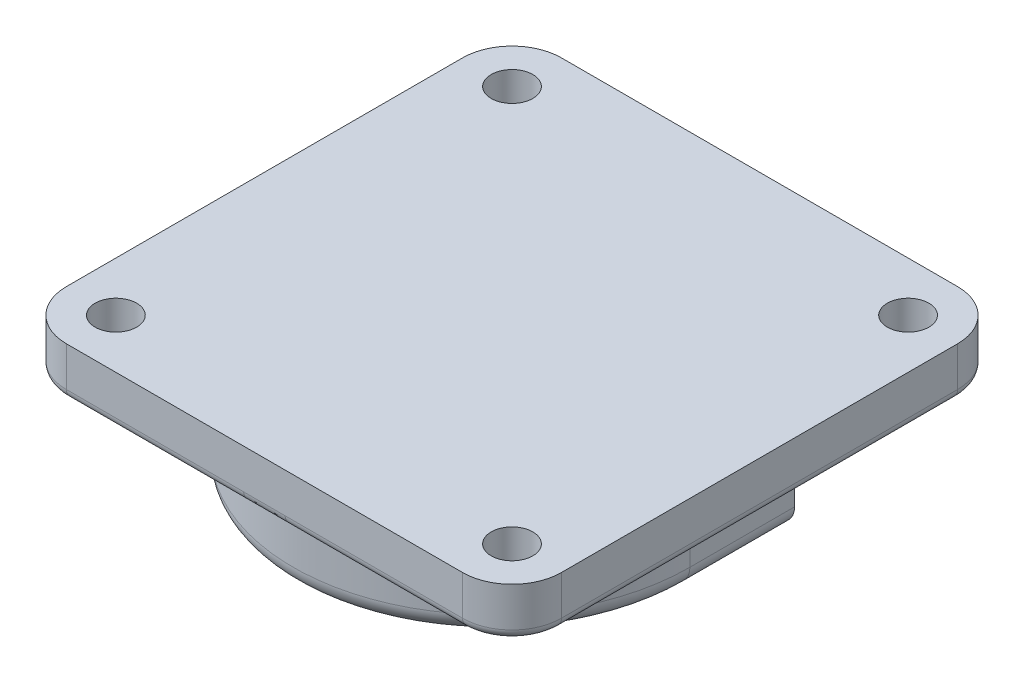
SolidWorks part; units mm, degrees
ref_plane "Front Plane" through (0, 0, 0) normal (0, 0, 1) x (1, 0, 0)
ref_plane "Top Plane" through (0, 0, 0) normal (0, 1, 0) x (1, 0, 0)
ref_plane "Right Plane" through (0, 0, 0) normal (1, 0, 0) x (0, 0, -1)
sketch "Sketch1" plane through (0, 0, 0) normal (0, 1, 0) x (1, 0, 0)
  line L0 (0, 11.4059) -> (0, -65.5477)
  line L1 (-20, 0) -> (20, 0)
  line L2 (17.052, -27.0709) -> (17.052, -16.496)
  line L3 (-20, -50) -> (20, -50)
  line L4 (25, -5) -> (25, -45)
  line L5 (17.052, -16.496) -> (20.0291, -16.496)
  line L6 (20.0291, -16.496) -> (20.0291, -27.0709)
  line L7 (-17.052, -16.496) -> (-20.0291, -16.496)
  line L8 (-25, -5) -> (-25, -45)
  line L9 (-17.052, -27.0709) -> (-17.052, -16.496)
  line L10 (-20.0291, -16.496) -> (-20.0291, -27.0709)
  arc A0 (25, -5) -> (20, 0) centre (20, -5) ccw
  circle A1 centre (20, -5) radius 2.1
  arc A2 (25, -45) -> (20, -50) centre (20, -45) cw
  circle A3 centre (20, -45) radius 2.1
  arc A4 (-17.052, -27.0709) -> (17.052, -27.0709) centre (0, -27.0709) ccw
  arc A5 (-20.0291, -27.0709) -> (20.0291, -27.0709) centre (0, -27.0709) ccw
  circle A6 centre (-20, -45) radius 2.1
  arc A7 (-25, -45) -> (-20, -50) centre (-20, -45) ccw
  circle A8 centre (-20, -5) radius 2.1
  arc A9 (-25, -5) -> (-20, 0) centre (-20, -5) cw
  point P2 (0, 0)
  point P30 (0, -50)
  dimension "D1" = 5
  dimension "D2" = 5
extrude "Boss-Extrude1" add sketch "Sketch1" along normal blind 5 contours L1 A0 L4 A2 L3 A7 L8 A9
extrude "Cut-Extrude1" cut sketch "Sketch1<3>" along normal through all contours A3
sketch "Sketch1<3>" plane through (0, 0, 0) normal (0, 1, 0) x (1, 0, 0) same geometry as "Sketch1"
extrude "Cut-Extrude2" cut sketch "Sketch1<4>" along normal through all contours A1
sketch "Sketch1<4>" plane through (0, 0, 0) normal (0, 1, 0) x (1, 0, 0) same geometry as "Sketch1"
extrude "Cut-Extrude3" cut sketch "Sketch1<5>" along normal through all contours A8
sketch "Sketch1<5>" plane through (0, 0, 0) normal (0, 1, 0) x (1, 0, 0) same geometry as "Sketch1"
extrude "Cut-Extrude4" cut sketch "Sketch1<6>" along normal through all contours A6
sketch "Sketch1<6>" plane through (0, 0, 0) normal (0, 1, 0) x (1, 0, 0) same geometry as "Sketch1"
extrude "Boss-Extrude2" add sketch "Sketch1<8>" against normal blind 8 contours A5 L6 L5 L2 A4 L9 L7 L10
sketch "Sketch1<8>" plane through (0, 0, 0) normal (0, 1, 0) x (1, 0, 0) same geometry as "Sketch1"
fillet "Fillet1" radius 2 3 edges at (-20.0291, 0, 21.7835) (20.0291, 0, 21.7835) (0, 0, 47.1)
fillet "Fillet2" radius 2 1 edges at (17.052, -4, 16.496)
fillet "Fillet3" radius 2 1 edges at (-17.052, -4, 16.496)
fillet "Fillet4" radius 2 3 edges at (-20.0291, -8, 21.7835) (0, -8, 47.1) (20.0291, -8, 21.7835)
fillet "Fillet5" radius 1 8 edges at (-23.5355, 0, 1.4645) (23.5355, 0, 1.4645) (25, 0, 25) (23.5355, 0, 48.5355) (0, 0, 50) (-23.5355, 0, 48.5355) (-25, 0, 25) (0, 0, 0)
chamfer "Chamfer1" distance 2 angle 45 4 edges at (20, 0, 47.1) (-20, 0, 42.9) (-20, 0, 2.9) (20, 0, 7.1)
